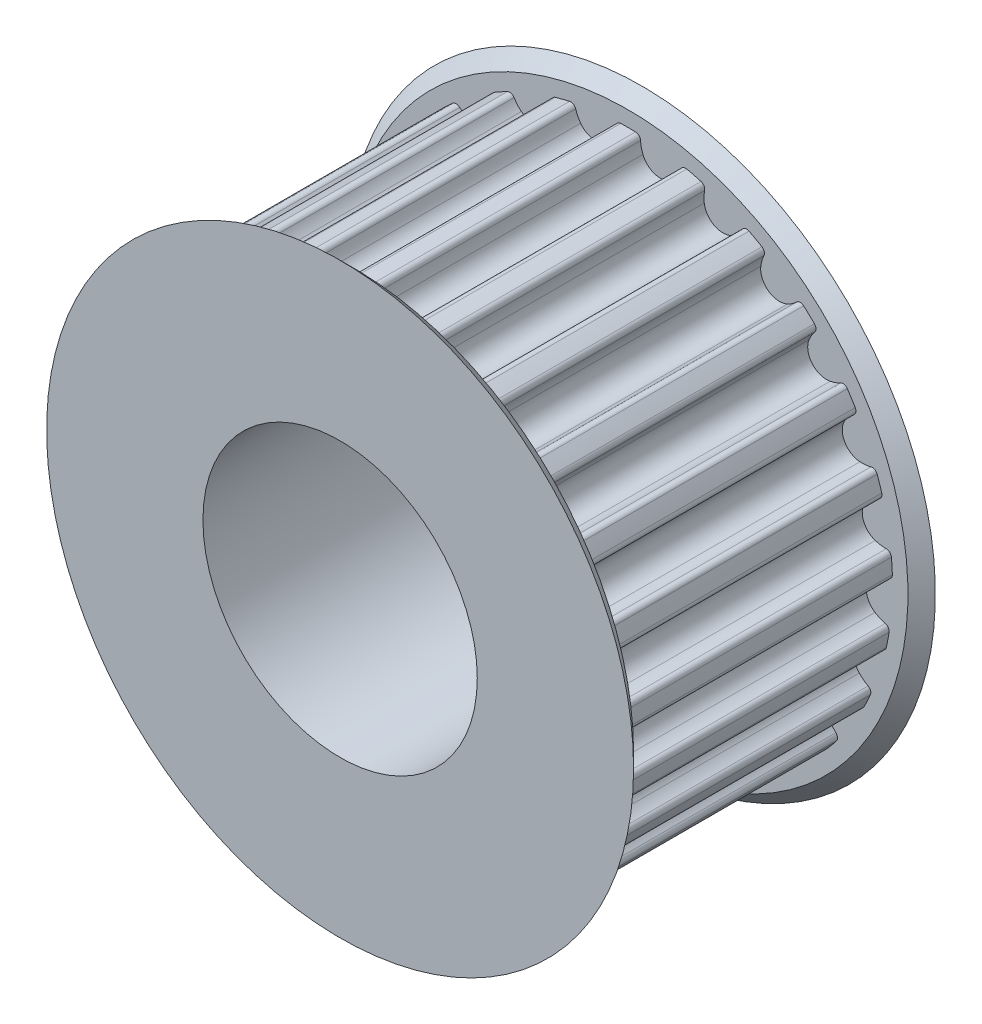
SolidWorks part; units mm, degrees
ref_plane "Front Plane" through (0, 0, 0) normal (0, 0, 1) x (1, 0, 0)
ref_plane "Top Plane" through (0, 0, 0) normal (0, 1, 0) x (1, 0, 0)
ref_plane "Right Plane" through (0, 0, 0) normal (1, 0, 0) x (0, 0, -1)
sketch "Sketch1" plane through (0, 0, 0) normal (0, 0, 1) x (1, 0, 0)
  circle A0 centre (0, 0) radius 7.9577
  dimension "D1" = 15.9155
extrude "Boss-Extrude1" add sketch "Sketch1" along normal mid plane 8
sketch "Sketch3" plane through (0, 0, 4) normal (0, 0, 1) x (1, 0, 0)
  line L0 (0, 0) -> (0, 7.9577) construction
  line L1 (0, 0) -> (0.872, 6.9029) construction
  line L2 (0, 7.9577) -> (0, 7.7077)
  line L3 (1.3928, 7.8349) -> (1.3593, 7.6143) construction
  line L4 (0.9974, 7.895) -> (1.3928, 7.8349)
  line L5 (0.872, 6.9029) -> (0.9974, 7.895) construction
  line L6 (1.979, 7.7077) -> (1.9168, 7.4656)
  circle A0 centre (0, 0) radius 7.9577 construction
  arc A1 (0, 7.7077) -> (0.215, 7.7047) centre (0, 0) cw
  circle A2 centre (0, 0) radius 7.9577
  circle A3 centre (0, 0) radius 7.9577
  arc A4 (0.215, 7.7047) -> (0.3607, 7.5626) centre (0.2109, 7.5548) cw
  arc A5 (0.3607, 7.5626) -> (0.4297, 7.2459) centre (1.3593, 7.6143) ccw
  arc A6 (0.4297, 7.2459) -> (1.3858, 7.1251) centre (0.941, 7.4485) ccw
  arc A7 (1.9168, 7.4656) -> (1.7078, 7.5162) centre (0, 0) ccw
  arc A8 (1.7078, 7.5162) -> (1.5314, 7.4147) centre (1.6746, 7.3699) ccw
  arc A9 (1.5314, 7.4147) -> (1.3858, 7.1251) centre (0.577, 7.7132) cw
  dimension "D4" = 0.15
  dimension "D5" = 1
  dimension "D7" = 0.55
  dimension "D1" = 7.2
  dimension "D3" = 0.25
  dimension "D6" = 0.4
  dimension "D8" = 1
  dimension "D2" = 0
extrude "Cut-Extrude1" cut sketch "Sketch3" against normal up to surface (8 mm away) contours A9 A8 A7 L6 L5 L4 L2 A1 A4 A5 A6 | L5 L4
pattern_circular "CirPattern1" count 25 over 360 about axis through (0, 0, 0) along (0, 0, 1) of "Cut-Extrude1"
sketch "Sketch4" plane through (0, 0, 4) normal (0, 0, 1) x (1, 0, 0)
  circle A0 centre (0, 0) radius 8.5577
  dimension "D1" = 17.1155
extrude "Boss-Extrude2" add sketch "Sketch4" along normal blind 0.4
mirror "Mirror1" about plane through (0, 0, 0) normal (0, 0, 1) of "Boss-Extrude2"
chamfer "Chamfer1" distance 0.4 angle 45 2 edges at (8.5577, 0, -4) (8.5577, 0, 4)
sketch "Sketch5" plane through (0, 0, 4.4) normal (0, 0, 1) x (1, 0, 0)
  circle A0 centre (0, 0) radius 4
  dimension "D1" = 8
extrude "Cut-Extrude2" cut sketch "Sketch5" against normal through all
sketch "Sketch7" plane through (0, 0, 4.4) normal (0, 0, 1) x (1, 0, 0)
  circle A0 centre (0, 0) radius 6
  circle A1 centre (0, 0) radius 4 construction
  circle A2 centre (0, 0) radius 4
  dimension "D1" = 12
equation "\"n\" = 25'teeth number"
equation "\"p\"= 2mm'tooth spacing"
equation "\"pd\"= \"n\" * \"p\" / pi"
equation "\"D1@Sketch1\"=\"pd\""
equation "\"halfToothAngle\"= 180 / \"n\""
equation "\"D1@Sketch3\"=\"halfToothAngle\""
equation "\"D1@CirPattern1\"=\"n\""
equation "\"flangeDia\"= \"pd\" + 1.2"
equation "\"D1@Sketch4\"=\"flangeDia\""
